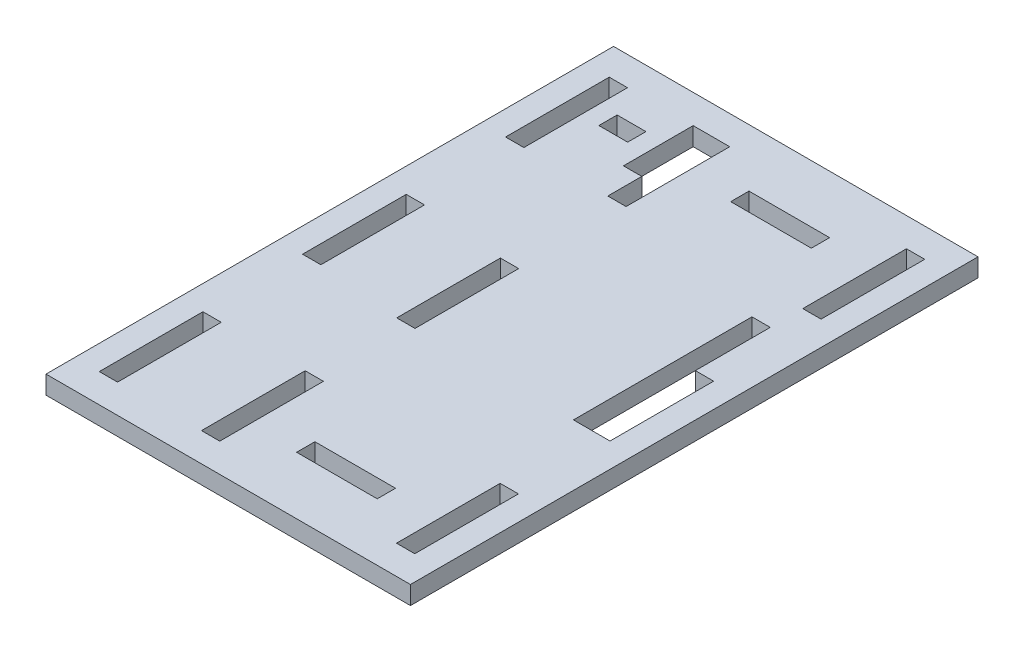
SolidWorks part; units mm, degrees
ref_plane "Front Plane" through (0, 0, 0) normal (0, 0, 1) x (1, 0, 0)
ref_plane "Top Plane" through (0, 0, 0) normal (0, 1, 0) x (1, 0, 0)
ref_plane "Right Plane" through (0, 0, 0) normal (1, 0, 0) x (0, 0, -1)
sketch "Sketch2" plane through (0, 0, 0) normal (0, 1, 0) x (1, 0, 0)
  line L1 (-27.3923, -44.2755) -> (27.3923, -44.2755)
  line L2 (-27.3923, -44.2755) -> (-27.3923, 44.2755)
  line L3 (-27.3923, 44.2755) -> (27.3923, 44.2755)
  line L4 (27.3923, -44.2755) -> (27.3923, 44.2755)
  line L5 (-27.3923, -44.2755) -> (27.3923, 44.2755) construction
  line L6 (-27.3923, 44.2755) -> (27.3923, -44.2755) construction
  point P0 (0, 0)
  dimension "D1" = 54.7846
  dimension "D2" = 88.551
extrude "Boss-Extrude1" add sketch "Sketch2" along normal blind 3.175
sketch "Sketch7" plane through (0, 3.175, 0) normal (0, 1, 0) x (1, 0, 0)
  line L0 (-27.3923, 44.2755) -> (-27.3923, -44.2755) construction
  line L1 (-27.3923, 44.2755) -> (-24.2173, 44.2755)
  line L2 (-27.3923, 44.2755) -> (-27.3923, 26.2755)
  line L3 (-27.3923, 26.2755) -> (-24.2173, 26.2755)
  line L4 (-24.2173, 44.2755) -> (-24.2173, 26.2755)
  line L5 (-27.3923, 9.0255) -> (-24.2173, 9.0255)
  line L6 (-27.3923, 9.0255) -> (-27.3923, -8.9745)
  line L7 (-27.3923, -8.9745) -> (-24.2173, -8.9745)
  line L8 (-24.2173, 9.0255) -> (-24.2173, -8.9745)
  line L9 (-27.3923, -44.2755) -> (27.3923, -44.2755) construction
  line L10 (-27.3923, -26.2755) -> (-24.2173, -26.2755)
  line L11 (-27.3923, -26.2755) -> (-27.3923, -44.2755)
  line L12 (-27.3923, -44.2755) -> (-24.2173, -44.2755)
  line L13 (-24.2173, -26.2755) -> (-24.2173, -44.2755)
  line L14 (27.3923, -44.2755) -> (27.3923, 44.2755) construction
  line L15 (27.3923, -44.2755) -> (24.2173, -44.2755)
  line L16 (27.3923, -44.2755) -> (27.3923, -26.2755)
  line L17 (27.3923, -26.2755) -> (24.2173, -26.2755)
  line L18 (24.2173, -44.2755) -> (24.2173, -26.2755)
  line L19 (27.3923, -10.3745) -> (24.2173, -10.3745)
  line L20 (27.3923, -10.3745) -> (27.3923, 7.6255)
  line L21 (27.3923, 7.6255) -> (24.2173, 7.6255)
  line L22 (24.2173, -10.3745) -> (24.2173, 7.6255)
  line L23 (27.3923, 44.2755) -> (-27.3923, 44.2755) construction
  line L24 (24.2173, -10.3745) -> (21.0423, -10.3745)
  line L25 (24.2173, -10.3745) -> (24.2173, 20.6255)
  line L26 (24.2173, 20.6255) -> (21.0423, 20.6255)
  line L27 (21.0423, -10.3745) -> (21.0423, 20.6255)
  line L28 (27.3923, 44.2755) -> (24.2173, 44.2755)
  line L29 (27.3923, 44.2755) -> (27.3923, 26.2755)
  line L30 (27.3923, 26.2755) -> (24.2173, 26.2755)
  line L31 (24.2173, 44.2755) -> (24.2173, 26.2755)
  line L32 (-12.8173, 44.2755) -> (-9.6423, 44.2755)
  line L33 (-12.8173, 44.2755) -> (-12.8173, 32.1755)
  line L34 (-12.8173, 32.1755) -> (-9.6423, 32.1755)
  line L35 (-9.6423, 44.2755) -> (-9.6423, 32.1755)
  line L37 (-9.6423, 44.2755) -> (-6.4673, 44.2755)
  line L38 (-9.6423, 44.2755) -> (-9.6423, 26.2755)
  line L39 (-9.6423, 26.2755) -> (-6.4673, 26.2755)
  line L40 (-6.4673, 44.2755) -> (-6.4673, 26.2755)
  line L41 (-21.0173, 39.2755) -> (-16.0173, 39.2755)
  line L42 (-21.0173, 39.2755) -> (-21.0173, 36.1005)
  line L43 (-21.0173, 36.1005) -> (-16.0173, 36.1005)
  line L44 (-16.0173, 39.2755) -> (-16.0173, 36.1005)
  line L45 (1.875, 39.2755) -> (15.875, 39.2755)
  line L46 (1.875, 39.2755) -> (1.875, 36.1005)
  line L47 (1.875, 36.1005) -> (15.875, 36.1005)
  line L48 (15.875, 39.2755) -> (15.875, 36.1005)
  line L49 (-9.6423, 7.6255) -> (-6.4673, 7.6255)
  line L50 (-9.6423, 7.6255) -> (-9.6423, -10.3745)
  line L51 (-9.6423, -10.3745) -> (-6.4673, -10.3745)
  line L52 (-6.4673, 7.6255) -> (-6.4673, -10.3745)
  line L53 (-9.6423, -26.2755) -> (-6.4673, -26.2755)
  line L54 (-9.6423, -26.2755) -> (-9.6423, -44.2755)
  line L55 (-9.6423, -44.2755) -> (-6.4673, -44.2755)
  line L56 (-6.4673, -26.2755) -> (-6.4673, -44.2755)
  line L57 (1.875, -36.1005) -> (15.875, -36.1005)
  line L58 (1.875, -36.1005) -> (1.875, -39.2755)
  line L59 (1.875, -39.2755) -> (15.875, -39.2755)
  line L60 (15.875, -36.1005) -> (15.875, -39.2755)
  line M29 (27.3923, -44.2755) -> (27.3923, 44.2755)
  line M30 (27.3923, 44.2755) -> (-27.3923, 44.2755)
  line M31 (-27.3923, 44.2755) -> (-27.3923, -44.2755)
  line M32 (-27.3923, -44.2755) -> (27.3923, -44.2755)
  dimension "D1" = 3.175
  dimension "D2" = 3.175
  dimension "D3" = 3.175
  dimension "D4" = 3.175
  dimension "D5" = 3.175
  dimension "D6" = 3.175
  dimension "D7" = 3.175
  dimension "D8" = 3.175
  dimension "D9" = 3.175
  dimension "D10" = 3.175
  dimension "D11" = 3.175
  dimension "D12" = 3.175
  dimension "D13" = 3.175
  dimension "D14" = 3.175
  dimension "D15" = 0
  dimension "D16" = 0
  dimension "D17" = 18
  dimension "D18" = 18
  dimension "D19" = 18
  dimension "D20" = 18
  dimension "D21" = 18
  dimension "D22" = 18
  dimension "D23" = 17.25
  dimension "D24" = 3.2
  dimension "D25" = 12.1
  dimension "D26" = 5
  dimension "D27" = 5
  dimension "D28" = 11.4
  dimension "D29" = 18
  dimension "D30" = 18
  dimension "D31" = 18
  dimension "D32" = 18.65
  dimension "D33" = 18.65
  dimension "D34" = 31
  dimension "D35" = 14
  dimension "D36" = 8.3423
  dimension "D37" = 5
  dimension "D38" = 0
  dimension "D39" = 5
  dimension "D40" = 14
extrude "Cut-Extrude1" cut sketch "Sketch7" against normal blind 10 contours L4 L3 M30 M31 | L44 L41 L42 L43 | L35 L33 L34 M30 | L40 L35 L38 L39 M30 | L48 L45 L46 L47 | L31 L30 M30 M29 | L27 L24 L22 L25 L26 | L22 L19 L21 M29 | L52 L49 L50 L51 | L8 L5 L7 M31 | L13 L10 M31 M32 | L56 L53 L54 M32 | L60 L57 L58 L59 | L18 L17 L16 L15 region at (-25.8048, 3.175, -35.2755) region at (-11.2298, 3.175, -38.2255) region at (-25.8048, 3.175, -0.0255) region at (-8.0548, 3.175, -35.2755) region at (-25.8048, 3.175, 35.2755) region at (25.8048, 3.175, -35.2755) region at (-8.0548, 3.175, 35.2755) region at (25.8048, 3.175, 1.3745) region at (22.6298, 3.175, -5.1255) region at (-18.5173, 3.175, -37.688) region at (8.875, 3.175, -37.688) region at (-8.0548, 3.175, 1.3745) region at (8.875, 3.175, 37.688)
sketch "Sketch8" plane through (0, 3.175, 0) normal (0, 1, 0) x (1, 0, 0)
  line L0 (-21.9075, 44.2755) -> (-29.828, 44.2755)
  line L1 (-12.8173, 44.2755) -> (-24.2173, 44.2755) construction
  line L2 (-31.6423, -49.2755) -> (31.6423, -49.2755)
  line L3 (-27.3923, 23.9387) -> (-27.3923, 30.5391)
  line L4 (-31.6423, -49.2755) -> (-31.6423, 49.2755)
  line L9 (-27.3923, 26.2755) -> (-27.3923, 9.0255) construction
  line L11 (-31.6423, 49.2755) -> (31.6423, 49.2755)
  line L12 (31.6423, -49.2755) -> (31.6423, 49.2755)
  line L13 (-31.6423, -49.2755) -> (31.6423, 49.2755) construction
  line L14 (-31.6423, 49.2755) -> (31.6423, -49.2755) construction
  line L15 (27.3923, -44.2755) -> (-27.3923, -44.2755)
  line L16 (27.3923, -44.2755) -> (27.3923, 44.2755)
  line L17 (27.3923, 44.2755) -> (-27.3923, 44.2755)
  line L18 (-27.3923, -44.2755) -> (-27.3923, 44.2755)
  line L19 (27.3923, -44.2755) -> (-27.3923, 44.2755) construction
  line L20 (27.3923, 44.2755) -> (-27.3923, -44.2755) construction
  point P0 (0, 0)
  point P8 (0, 0)
  point P15 (0, 0)
  line M23 (-12.8173, 44.2755) -> (-24.2173, 44.2755)
  line M26 (-27.3923, 26.2755) -> (-27.3923, 9.0255)
  line M30 (-27.3923, -8.9745) -> (-27.3923, -26.2755)
  line M33 (-24.2173, -44.2755) -> (-9.6423, -44.2755)
  line M37 (-6.4673, -44.2755) -> (24.2173, -44.2755)
  line M40 (27.3923, -26.2755) -> (27.3923, -10.3745)
  line M46 (27.3923, 7.6255) -> (27.3923, 26.2755)
  line M49 (24.2173, 44.2755) -> (-6.4673, 44.2755)
extrude "Boss-Extrude2" add sketch "Sketch8" against normal up to surface (3.175 mm away) contours L2 L12 L11 L4 L15 L18 L3 L0 L17 L16 M30 M26 M23 M49 M46 M40 M37 M33 region at (-30.4711, 3.175, 0) up to face at (-1.4996, 0, -3.1314)
